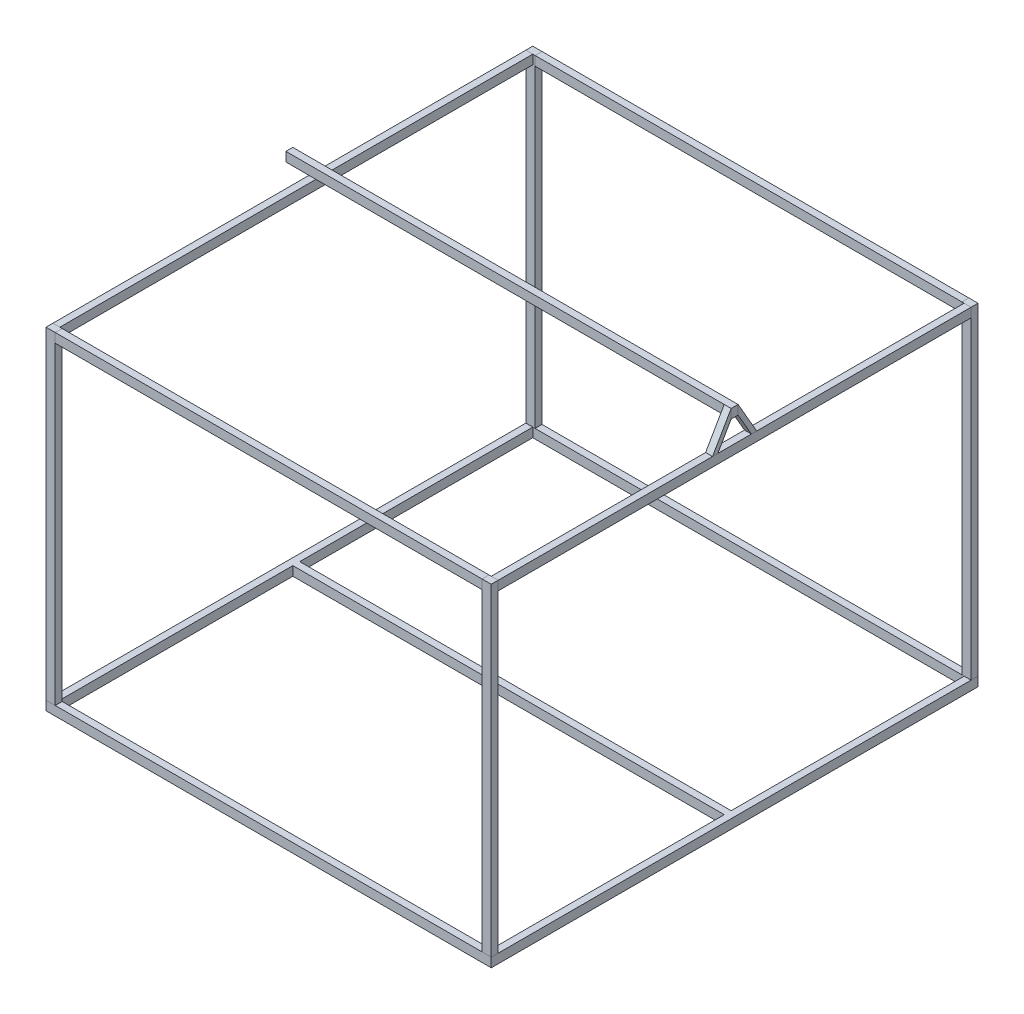
SolidWorks part; units mm, degrees
ref_plane "Front Plane" through (0, 0, 0) normal (0, 0, 1) x (1, 0, 0)
ref_plane "Top Plane" through (0, 0, 0) normal (0, 1, 0) x (1, 0, 0)
ref_plane "Right Plane" through (0, 0, 0) normal (1, 0, 0) x (0, 0, -1)
other "Configuration Table"
sketch "MetalBase" plane through (0, 0, 0) normal (0, 1, 0) x (1, 0, 0)
  line L0 (-60, -60) -> (7660, -60)
  line L1 (0, 0) -> (7600, 0)
  line L2 (0, 0) -> (0, 2020)
  line L3 (0, 4100) -> (7600, 4100)
  line L4 (7600, 0) -> (7600, 2020)
  line L5 (7660, -60) -> (7660, 4160)
  line L6 (-60, 4160) -> (7660, 4160)
  line L7 (-60, -60) -> (-60, 4160)
  line L8 (0, 2050) -> (7600, 2050) construction
  line L9 (0, 2020) -> (7600, 2020)
  line L10 (0, 2080) -> (7600, 2080)
  line L11 (0, 2080) -> (0, 4100)
  line L12 (7600, 2080) -> (7600, 4100)
  line L13 (0, 0) -> (0, 4100) construction
  line L15 (7600, 0) -> (7600, 4100) construction
  point P15 (7660, 2050)
  dimension "D1" = 4100
  dimension "D2" = 7600
  dimension "D6" = 4220
  dimension "D7" = 7720
  dimension "D3" = 60
  dimension "D4" = 30
  dimension "D5" = 30
sketch "InternalSpace" plane through (0, 0, 0) normal (0, 1, 0) x (1, 0, 0)
  line L26 (50, 50) -> (7550, 50)
  line L27 (7550, 50) -> (7550, 4050)
  line L28 (7550, 4050) -> (50, 4050)
  line L29 (50, 4050) -> (50, 50)
  line L30 (50, 50) -> (7550, 50)
  line L31 (7550, 50) -> (7550, 4050)
  line L32 (7550, 4050) -> (50, 4050)
  line L33 (50, 4050) -> (50, 50)
  dimension "D2" = 4000
  dimension "D3" = 7500
  dimension "D1" = 110
sketch "Furniture" plane through (0, 0, 0) normal (0, 1, 0) x (1, 0, 0)
  line L0 (6750, 2050) -> (6750, 4050)
  line L1 (2200, 2550) -> (1400, 2550)
  line L2 (2200, 2550) -> (2200, 4050)
  line L3 (2200, 4050) -> (1400, 4050)
  line L4 (1400, 2550) -> (1400, 4050)
  line L5 (1050, 50) -> (50, 50)
  line L6 (1050, 50) -> (1050, 2050)
  line L7 (1050, 2050) -> (50, 2050)
  line L8 (50, 50) -> (50, 2050)
  line L9 (6350, 2110) -> (7550, 2110)
  line L10 (2200, 4050) -> (2200, 150)
  line L11 (0, 0) -> (7600, 0) construction
  line L12 (6350, 50) -> (6350, 2110)
  line L13 (6470, 50) -> (6470, 1990)
  line L15 (2200, 2050) -> (7550, 2050) construction
  line L17 (1979.5569, 919.0285) -> (2200, 150)
  line L18 (6350, 150) -> (5722.0427, 459.305)
  line L19 (6710, 1120.0467) -> (7310, 1120.0467)
  line L24 (6710, 1120.0467) -> (6710, 1880.0467)
  line L25 (6710, 1880.0467) -> (7310, 1880.0467)
  line L26 (7310, 1120.0467) -> (7310, 1880.0467)
  line L27 (6350, 2110) -> (5750, 2110)
  line L28 (6350, 2110) -> (6350, 1510)
  line L29 (6350, 1510) -> (5750, 1510)
  line L30 (5750, 2110) -> (5750, 1510)
  line L31 (2320, 2050) -> (4320, 2050) construction
  line L32 (4320, 2050) -> (4320, 4050) construction
  line L33 (2200, 150) -> (2499.3532, 150) construction
  line L34 (2499.3532, 150) -> (2499.3532, 981.1813) construction
  line L35 (2499.3532, 981.1813) -> (2200, 981.1813) construction
  line L36 (2320, 4050) -> (2320, 150)
  line L37 (2200, 150) -> (2200, 50)
  line L38 (50, 50) -> (7550, 50) construction
  line L39 (2320, 150) -> (2320, 50)
  line L40 (7550, 4050) -> (50, 4050) construction
  line L41 (7550, 50) -> (7550, 4050) construction
  line L42 (50, 4050) -> (50, 50) construction
  line L43 (7550, 4050) -> (50, 4050) construction
  line L44 (7550, 50) -> (7550, 4050) construction
  line L45 (50, 50) -> (7550, 50) construction
  line L46 (50, 4050) -> (50, 50) construction
  line L47 (7010, 1120.0467) -> (7010, 1445.9123) construction
  line L48 (6470, 1990) -> (7550, 1990)
  line L49 (-60, -60) -> (-60, 4160) construction
  line L50 (7550, 809.8905) -> (7383.7397, 809.8905)
  line L51 (7550, 809.8905) -> (7550, 230.8186)
  line L52 (7550, 230.8186) -> (7383.7397, 230.8186)
  line L53 (7283.7397, 709.8905) -> (7283.7397, 330.8186)
  line L54 (7660, 4160) -> (-60, 4160) construction
  line L55 (-60, 4160) -> (-60, -60) construction
  line L56 (-60, -60) -> (7660, -60) construction
  line L57 (7660, -60) -> (7660, 4160) construction
  arc A1 (1979.5569, 919.0285) -> (1414.1883, 0) centre (2200, 150) ccw construction
  arc A2 (5722.0427, 459.305) -> (6350, 850) centre (6350, 150) cw construction
  arc A3 (7383.7397, 230.8186) -> (7283.7397, 330.8186) centre (7383.7397, 330.8186) cw
  arc A4 (7383.7397, 809.8905) -> (7283.7397, 709.8905) centre (7383.7397, 709.8905) ccw
  point P56 (7010, 1990)
  dimension "D13" = 600
  dimension "D21" = 100
  dimension "D1" = 1500
  dimension "D2" = 800
  dimension "D3" = 2000
  dimension "D4" = 1000
  dimension "D5" = 100
  dimension "D6" = 60
  dimension "D7" = 700
  dimension "D8" = 600
  dimension "D9" = 2260
  dimension "D10" = 800
  dimension "D11" = 100
  dimension "D12" = 760
  dimension "D14" = 2000
  dimension "D15" = 800
  dimension "D16" = 2000
  dimension "D17" = 600
  dimension "D18" = 60
  dimension "D19" = 4150
  dimension "D20" = 120
  dimension "D22" = 120
  dimension "D23" = 110
  dimension "D25" = 4220
  dimension "D26" = 1200
  dimension "D27" = 4030
  dimension "D24" = 110
sketch "Metal frame" plane through (0, 0, 0) normal (0, 1, 0) x (1, 0, 0)
  line L0 (0, 4100) -> (7600, 4100) construction
  line L1 (0, 4100) -> (7600, 4100)
  line L3 (0, 0) -> (0, 2020)
  line L4 (0, 0) -> (7600, 0) construction
  line L5 (0, 0) -> (7600, 0)
  line L7 (7600, 0) -> (7600, 2020)
  line L8 (-60, 4160) -> (7660, 4160)
  line L9 (7660, -60) -> (7660, 4160)
  line L10 (-60, -60) -> (7660, -60)
  line L11 (-60, -60) -> (-60, 4160)
  line L12 (0, 2050) -> (62.1159, 2050) construction
  line L13 (7600, 2080) -> (0, 2080)
  line L15 (7600, 2020) -> (0, 2020)
  line L17 (7600, 2080) -> (7600, 4100)
  line L18 (0, 2080) -> (0, 4100)
  line L19 (7600, 0) -> (7600, 4100) construction
  line L21 (0, 0) -> (0, 4100) construction
  point P14 (-60, 2050)
  dimension "D2" = 7720
  dimension "D3" = 4220
  dimension "D4" = 60
  dimension "D1" = 60
sketch "Walls bottom" plane through (0, 0, 0) normal (0, 1, 0) x (1, 0, 0)
  line L0 (-60, 4160) -> (7660, 4160) construction
  line L2 (-60, -60) -> (7660, -60) construction
  line L3 (7660, -60) -> (7660, 4160) construction
  line L4 (-60, -60) -> (-60, 4160) construction
  line L5 (-60, -60) -> (7660, -60)
  line L6 (7660, -60) -> (7660, 4160)
  line L7 (-60, 4160) -> (7660, 4160)
  line L8 (-60, -60) -> (-60, 4160)
  line L9 (40, 40) -> (40, 4060)
  line L10 (40, 4060) -> (7560, 4060)
  line L11 (7560, 40) -> (7560, 4060)
  line L12 (40, 40) -> (7560, 40)
  dimension "D2" = 4020
  dimension "D3" = 7520
  dimension "D4" = 7720
  dimension "D5" = 4220
  dimension "D1" = 100
sketch "Sketch15" plane through (0, 0, 0) normal (0, 1, 0) x (1, 0, 0)
  line L2 (7550, 50) -> (5502.4266, 50)
  line L3 (7550, 50) -> (7550, 1250)
  line L4 (7550, 1250) -> (5502.4266, 1250)
  line L5 (5502.4266, 50) -> (5502.4266, 1250)
  dimension "D1" = 1200
extrude "MetalFrame" add sketch "Metal frame" against normal blind 80 contours L11 L10 L9 L8 L15 L7 L5 L3 L13 L18 L1 L17 region at (3800, 0, -2050)
sketch "Sketch18" plane through (0, 0, 0) normal (0, 1, 0) x (1, 0, 0)
  line L0 (0, 0) -> (7600, 0) construction
  line L1 (3800, -1014.8769) -> (8467.9433, -1014.8769)
  line L2 (3800, -1014.8769) -> (3800, 5493.3133)
  line L3 (3800, 5493.3133) -> (8467.9433, 5493.3133)
  line L4 (8467.9433, -1014.8769) -> (8467.9433, 5493.3133)
  point P6 (3800, 0)
extrude "Cut-Extrude1" cut sketch "Sketch18" against normal through all
sketch "Sketch19" plane through (0, 0, 0) normal (0, 1, 0) x (1, 0, 0)
  line L0 (0, 0) -> (3800, 0) construction
  line L1 (3800, 4100) -> (3740, 4100)
  line L2 (3800, 4100) -> (3800, 0)
  line L3 (3800, 0) -> (3740, 0)
  line L4 (3740, 4100) -> (3740, 0)
  dimension "D1" = 60
extrude "Boss-Extrude1" add sketch "Sketch19" against normal blind 80
sketch "Sketch20" plane through (0, 0, 0) normal (1, 0, 0) x (0, 0, -1)
  line L0 (2050, 0) -> (2050, 3000) construction
  line L1 (4160, 0) -> (-60, 0) construction
  line L2 (4160, 0) -> (4160, 2800) construction
  line L3 (4160, 2800) -> (2050, 3000) construction
  line L4 (2050, 3000) -> (5424.8088, 3000) construction
  line L5 (4160, 2800) -> (4439.2907, 2773.5269) construction
  line L6 (4160, 150) -> (-211.81, 150) construction
  dimension "D1" = 2650
  dimension "D2" = 3000
  dimension "D3" = 150
  dimension "D4" = 2119.4575
  dimension "D5" = 2400
  dimension "D6" = 280.5425
  dimension "D7" = 2800
  dimension "D8" = 5.415
sketch "Sketch23" plane through (-60, 0, 0) normal (1, 0, 0) x (0, 0, -1)
  line L0 (2050, 0) -> (2050, 3000) construction
  line L1 (4160, 0) -> (4100, 0)
  line L2 (4160, 0) -> (4160, 2800)
  line L3 (4160, 2800) -> (4100, 2800)
  line L4 (4100, 0) -> (4100, 2800)
  line L5 (0, 0) -> (0, 2800)
  line L6 (-60, 2800) -> (0, 2800)
  line L7 (-60, 0) -> (-60, 2800)
  line L8 (-60, 0) -> (0, 0)
  line L10 (0, 2800) -> (4100, 2800)
  line L11 (0, 2800) -> (0, 2720)
  line L12 (0, 2720) -> (4100, 2720)
  line L13 (4100, 2800) -> (4100, 2720)
  line M8 (-60, 0) -> (4160, 0)
  dimension "D1" = 60
  dimension "D2" = 80
extrude "Boss-Extrude5" add sketch "Sketch23" along normal blind 80 separate body contours L4 L3 L2 M8 | L7 L6 L5 M8 region at (-60, 1400, -4130) region at (-60, 1400, 30)
extrude "Boss-Extrude6" add sketch "Sketch23<3>" along normal blind 60 separate body contours L0 L12 L5 L10 | L12 L0 L10 L4 region at (-60, 2760, -1025) region at (-60, 2760, -3075)
sketch "Sketch23<3>" plane through (-60, 0, 0) normal (1, 0, 0) x (0, 0, -1) same geometry as "Sketch23"
extrude "Boss-Extrude7" add sketch "Sketch23<5>" against normal blind 80 from surface separate body contours L4 L3 L2 M8 | L7 L6 L5 M8 region at (-60, 1400, -4130) region at (-60, 1400, 30) starting at face at (3800, -40, -2050)
sketch "Sketch23<5>" plane through (-60, 0, 0) normal (1, 0, 0) x (0, 0, -1) same geometry as "Sketch23"
extrude "Boss-Extrude8" add sketch "Sketch23<6>" against normal blind 60 from surface separate body contours L12 L0 L10 L4 | L0 L12 L5 L10 region at (-60, 2760, -1025) region at (-60, 2760, -3075) starting at face at (3800, 1400, 30)
sketch "Sketch23<6>" plane through (-60, 0, 0) normal (1, 0, 0) x (0, 0, -1) same geometry as "Sketch23"
sketch "Sketch24" plane through (0, 2800, 0) normal (0, 1, 0) x (1, 0, 0)
  line L1 (20, 4160) -> (3720, 4160)
  line L2 (20, 4160) -> (20, 4100)
  line L3 (20, 4100) -> (3720, 4100)
  line L4 (3720, 4160) -> (3720, 4100)
  line L5 (20, 0) -> (3720, 0)
  line L6 (20, 0) -> (20, -60)
  line L7 (20, -60) -> (3720, -60)
  line L8 (3720, 0) -> (3720, -60)
extrude "Boss-Extrude9" add sketch "Sketch24" against normal blind 80 separate body
sketch "Sketch25" plane through (3800, 0, 0) normal (1, 0, 0) x (0, 0, -1)
  line L0 (2050, 3000) -> (5424.8088, 3000) construction
  line L1 (2020, 3080) -> (2080, 3080)
  line L2 (2020, 3080) -> (2020, 3000)
  line L3 (2020, 3000) -> (2080, 3000)
  line L4 (2080, 3080) -> (2080, 3000)
  line L5 (2020, 3000) -> (1904.5299, 2800)
  line L6 (0, 2800) -> (4100, 2800) construction
  line L7 (2020, 3080) -> (1858.3419, 2800)
  line L8 (2050, 3000) -> (2050, 2907.5208) construction
  line L9 (2050, 0) -> (2050, 3000) construction
  line L10 (2080, 3000) -> (2195.4701, 2800)
  line L11 (2080, 3080) -> (2241.6581, 2800)
  point P6 (2050, 3000)
  line M8 (4100, 2800) -> (0, 2800)
  dimension "D1" = 60
  dimension "D2" = 80
  dimension "D3" = 40
extrude "Boss-Extrude10" add sketch "Sketch25" against normal blind 60 separate body contours L2 L7 L5 M8 | L11 L4 L10 M8 region at (3800, 2921.1111, -1950.0765) region at (3800, 2921.1111, -2149.9235)
extrude "Boss-Extrude11" add sketch "Sketch25<3>" against normal up to surface (3860 mm away) separate body contours L4 L1 L2 L3 region at (3800, 3040, -2050) up to face at (-60, 2760, -2050)
sketch "Sketch25<3>" plane through (3800, 0, 0) normal (1, 0, 0) x (0, 0, -1) same geometry as "Sketch25"
